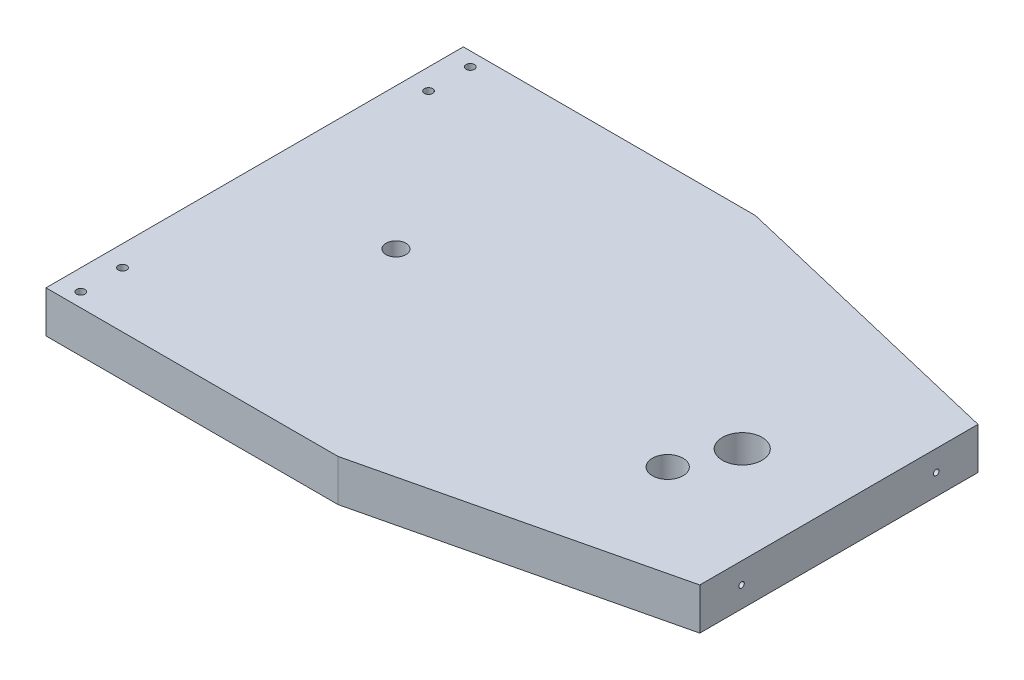
SolidWorks part; units mm, degrees
material "Carvalho"
ref_plane "Plano frontal" through (0, 0, 0) normal (0, 0, 1) x (1, 0, 0)
ref_plane "Plano superior" through (0, 0, 0) normal (0, 1, 0) x (1, 0, 0)
ref_plane "Plano direito" through (0, 0, 0) normal (1, 0, 0) x (0, 0, -1)
sketch "Esboço1" plane through (0, 0, 0) normal (0, 1, 0) x (1, 0, 0)
  line L0 (210, 50) -> (105, 75)
  line L1 (0, -75) -> (105, -75)
  line L2 (0, -75) -> (0, 75)
  line L3 (0, 75) -> (105, 75)
  line L4 (210, -50) -> (210, 50)
  line L7 (105, -75) -> (210, -50)
  line L8 (-14.8259, 0) -> (14.392, 0) construction
  line L9 (0, 21.2472) -> (0, -16.7598) construction
  circle A0 centre (50.8, 0) radius 3.5719
  circle A1 centre (175.26, 0) radius 7.14
  circle A2 centre (167.507, -19.0433) radius 5.5
  circle A3 centre (167.507, -19.0433) radius 4.5 construction
  circle A4 centre (7.5, -70) radius 1.5
  circle A5 centre (7.5, -55) radius 1.5
  circle A6 centre (7.5, -70) radius 1.5 construction
  circle A7 centre (7.5, -55) radius 1.5 construction
  circle A8 centre (7.5, 55) radius 1.5
  circle A9 centre (7.5, 70) radius 1.5
  point P0 (0, 0)
  dimension "D3" = 7.1437
  dimension "D5" = 14.28
  dimension "D9" = 1
  dimension "D1" = 25
  dimension "D2" = 150
  dimension "D4" = 50.8
  dimension "D6" = 210
  dimension "D7" = 175.26
  dimension "D8" = 105
extrude "Ressalto-extrusão1" add sketch "Esboço1" along normal blind 15
sketch "Esboço2" plane through (210, 0, 0) normal (1, 0, 0) x (0, 0, -1)
  line L0 (0, 15) -> (0, 0) construction
  line L1 (-50, 15) -> (50, 15) construction
  circle A0 centre (35, 7.5) radius 1
  circle A1 centre (-35, 7.5) radius 1
  point P9 (0, 7.5)
  dimension "D1" = 2
  dimension "D2" = 35
extrude "Corte-extrusão1" cut sketch "Esboço2" against normal blind 10
